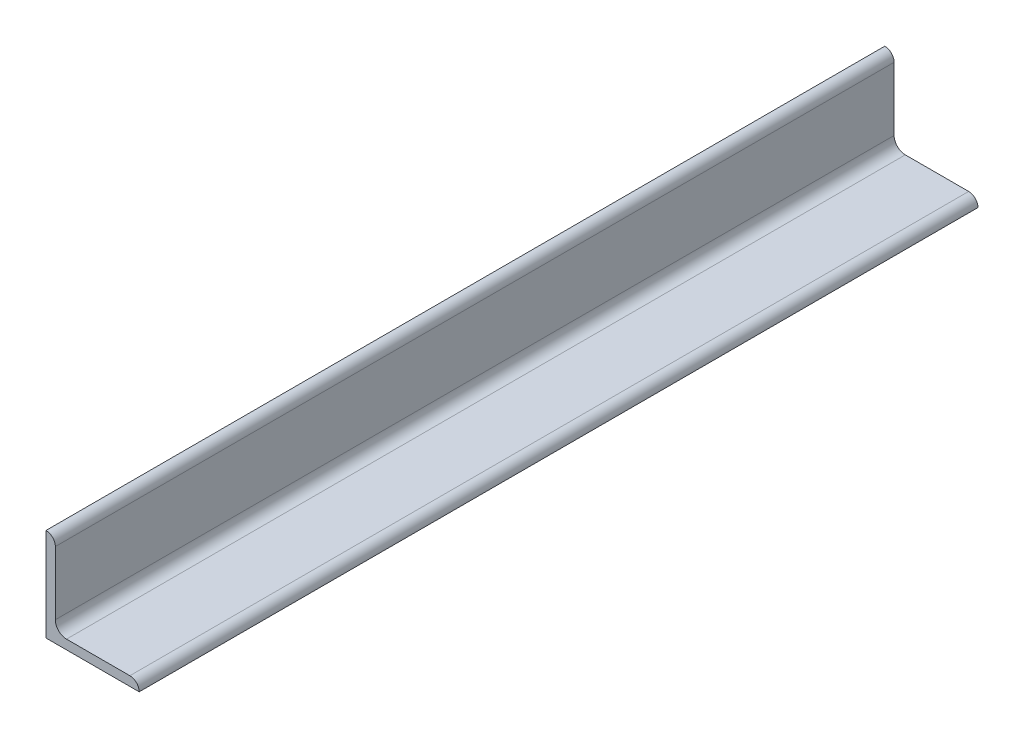
SolidWorks part; units mm, degrees
ref_plane "Plane1" through (0, 0, 0) normal (0, 0, 1) x (1, 0, 0)
ref_plane "Plane2" through (0, 0, 0) normal (0, 1, 0) x (1, 0, 0)
ref_plane "Plane3" through (0, 0, 0) normal (1, 0, 0) x (0, 0, -1)
sketch "Sketch1" plane through (0, 0, 0) normal (0, 0, 1) x (1, 0, 0)
  line L0 (0, 100) -> (0, 0)
  line L1 (0, 100) -> (9.525, 100) construction
  line L2 (10, 100) -> (10, 22)
  line L3 (22, 10) -> (100, 10)
  line L4 (100, 9.525) -> (100, 0) construction
  line L5 (100, 0) -> (0, 0)
  line L6 (100, 10) -> (100, 0)
  line L7 (0, 100) -> (10, 100)
  arc A2 (22, 10) -> (10, 22) centre (22, 22) cw
  dimension "Radius_1" = 12
  dimension "V_leg" = 100
  dimension "H_leg" = 100
extrude "BaseSteelAngle" add sketch "Sketch1" along normal mid plane 900
fillet "ToeFillet" radius 10 2 edges at (100, 10, 0) (10, 100, 0)
